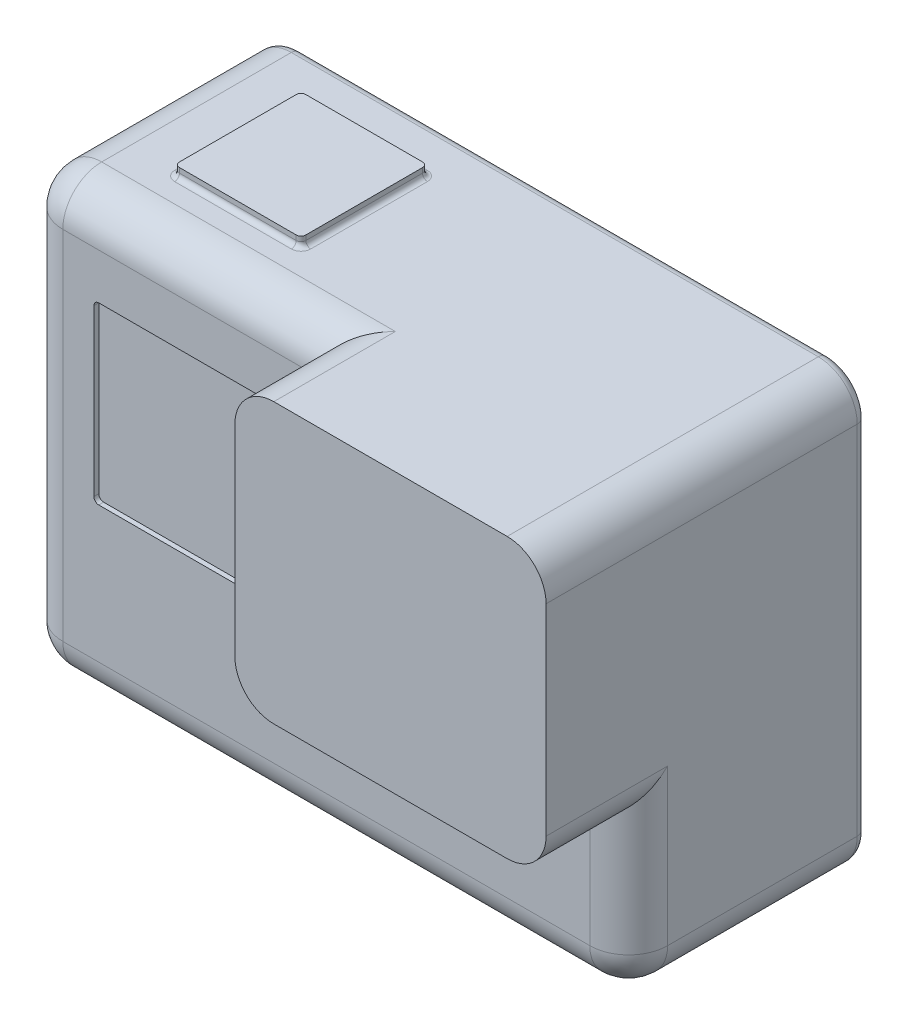
SolidWorks part; units mm, degrees
ref_plane "Alzado" through (0, 0, 0) normal (0, 0, 1) x (1, 0, 0)
ref_plane "Planta" through (0, 0, 0) normal (0, 1, 0) x (1, 0, 0)
ref_plane "Vista lateral" through (0, 0, 0) normal (1, 0, 0) x (0, 0, -1)
sketch "Croquis1" plane through (0, 0, 0) normal (0, 0, 1) x (1, 0, 0)
  line L1 (0, 0) -> (-62.2, 0)
  line L2 (0, 0) -> (0, 44.7)
  line L3 (0, 44.7) -> (-62.2, 44.7)
  line L4 (-62.2, 0) -> (-62.2, 44.7)
  dimension "D1" = 62.2
  dimension "D2" = 44.7
extrude "Saliente-Extruir1" add sketch "Croquis1" along normal blind 24.5
sketch "Croquis2" plane through (0, 0, 24.5) normal (0, 0, 1) x (1, 0, 0)
  line L1 (0, 44.7) -> (-32, 44.7)
  line L2 (0, 44.7) -> (0, 16)
  line L3 (0, 16) -> (-32, 16)
  line L4 (-32, 44.7) -> (-32, 16)
  dimension "D1" = 32
  dimension "D2" = 28.7
extrude "Saliente-Extruir2" add sketch "Croquis2" along normal blind 8.5
sketch "Croquis3" plane through (0, 0, 24.5) normal (0, 0, 1) x (1, 0, 0)
  line L0 (-32, 44.7) -> (-32, 16) construction
  line L1 (-55, 36) -> (-37, 36)
  line L2 (-55, 36) -> (-55, 18)
  line L3 (-55, 18) -> (-37, 18)
  line L4 (-37, 36) -> (-37, 18)
  line L6 (-62.2, 0) -> (0, 0) construction
  dimension "D1" = 5
  dimension "D2" = 18
  dimension "D3" = 18
  dimension "D4" = 18
extrude "Cortar-Extruir1" cut sketch "Croquis3" against normal blind 0.5
sketch "Croquis4" plane through (0, 44.7, 0) normal (0, 1, 0) x (1, 0, 0)
  line L0 (-62.2, -24.5) -> (-62.2, 0) construction
  line L1 (-40.2, -5) -> (-53.2, -5)
  line L2 (-40.2, -5) -> (-40.2, -18)
  line L3 (-40.2, -18) -> (-53.2, -18)
  line L4 (-53.2, -5) -> (-53.2, -18)
  line L5 (0, 0) -> (-62.2, 0) construction
  dimension "D1" = 13
  dimension "D2" = 13
  dimension "D3" = 9
  dimension "D4" = 5
extrude "Saliente-Extruir3" add sketch "Croquis4" along normal blind 1
fillet "Redondeo2" radius 0.5 12 edges at (-55, 18, 24.25) (-37, 18, 24.25) (-37, 36, 24.25) (-55, 36, 24.25) (-40.2, 44.7, 11.5) (-40.2, 45.2, 18) (-46.7, 44.7, 18) (-53.2, 45.2, 18) (-40.2, 45.2, 5) (-46.7, 44.7, 5) (-53.2, 44.7, 11.5) (-53.2, 45.2, 5)
fillet "Redondeo3" radius 1 4 edges at (-62.2, 22.35, 0) (-31.1, 0, 0) (-31.1, 44.7, 0) (0, 22.35, 0)
fillet "Redondeo1" radius 4 15 edges at (-31.1, 0, 24.5) (0, 8, 24.5) (0, 16, 28.75) (-32, 16, 28.75) (-32, 44.7, 28.75) (-62.2, 22.35, 24.5) (-47.1, 44.7, 24.5) (0, 44.7, 17) (0, 0, 12.75) (-62.2, 0, 12.75) (-62.2, 44.7, 12.75) (-61.9071, 44.4071, 0.2929) (-61.9071, 0.2929, 0.2929) (-0.2929, 0.2929, 0.2929) (-0.2929, 44.4071, 0.2929)
sketch "Croquis5" plane through (0, 0, 24.5) normal (0, 0, 1) x (1, 0, 0)
  line L12 (-58.2, 4) -> (-4, 4)
  line L13 (-4, 4) -> (-4, 16)
  line L14 (-4, 16) -> (-28, 16)
  line L15 (-32, 20) -> (-32, 40.7)
  line L16 (-32, 40.7) -> (-58.2, 40.7)
  line L17 (-58.2, 40.7) -> (-58.2, 4)
  line L18 (-58.2, 4) -> (-4, 4)
  line L19 (-4, 4) -> (-4, 16)
  line L20 (-4, 16) -> (-28, 16)
  line L21 (-32, 20) -> (-32, 40.7)
  line L22 (-32, 40.7) -> (-58.2, 40.7)
  line L23 (-58.2, 40.7) -> (-58.2, 4)
  arc A2 (-32, 20) -> (-28, 16) centre (-28, 20) ccw
  arc A3 (-32, 20) -> (-28, 16) centre (-28, 20) ccw
  dimension "D1" = 0
